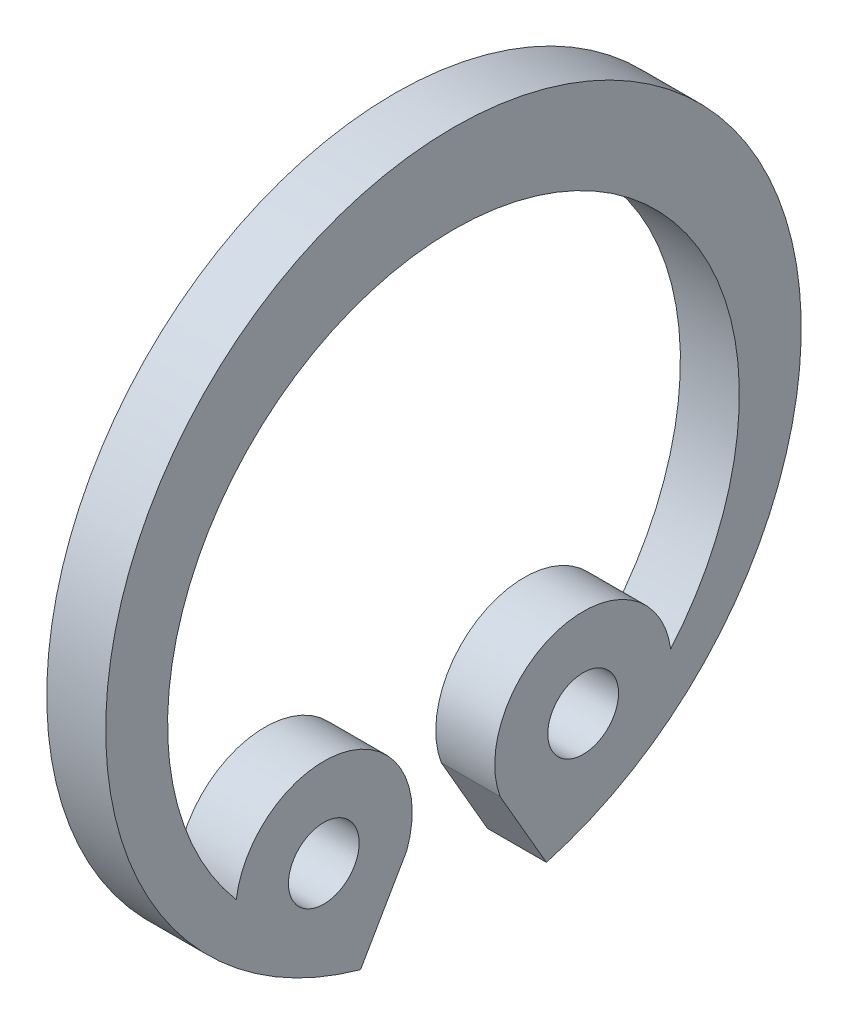
SolidWorks part; units mm, degrees
ref_plane "Front Plane" through (0, 0, 0) normal (0, 0, 1) x (1, 0, 0)
ref_plane "Top Plane" through (0, 0, 0) normal (0, 1, 0) x (1, 0, 0)
ref_plane "Right Plane" through (0, 0, 0) normal (1, 0, 0) x (0, 0, -1)
ref_plane "Plane1" through (0, 0, 0) normal (1, 0, 0) x (0, 0, -1)
sketch "Sketch1" plane through (0, 0, 0) normal (1, 0, 0) x (0, 0, -1)
  line L0 (-1.5759, -5.6856) -> (-0.7921, -4.3281)
  line L1 (0.7921, -4.3281) -> (1.5759, -5.6856)
  arc A0 (1.5759, -5.6856) -> (-1.5759, -5.6856) centre (0, 0) ccw
  arc A1 (-0.7921, -4.3281) -> (-3.6855, -3.6027) centre (-2.2, -3.8105) ccw
  arc A2 (-3.6855, -3.6027) -> (3.6855, -3.6027) centre (0, -0.45) cw
  arc A3 (3.6855, -3.6027) -> (0.7921, -4.3281) centre (2.2, -3.8105) ccw
  circle A4 centre (2.2, -3.8105) radius 0.6
  circle A5 centre (-2.2, -3.8105) radius 0.6
extrude "Boss-Extrude1" add sketch "Sketch1" against normal blind 0.5 and the other way blind 0.5
